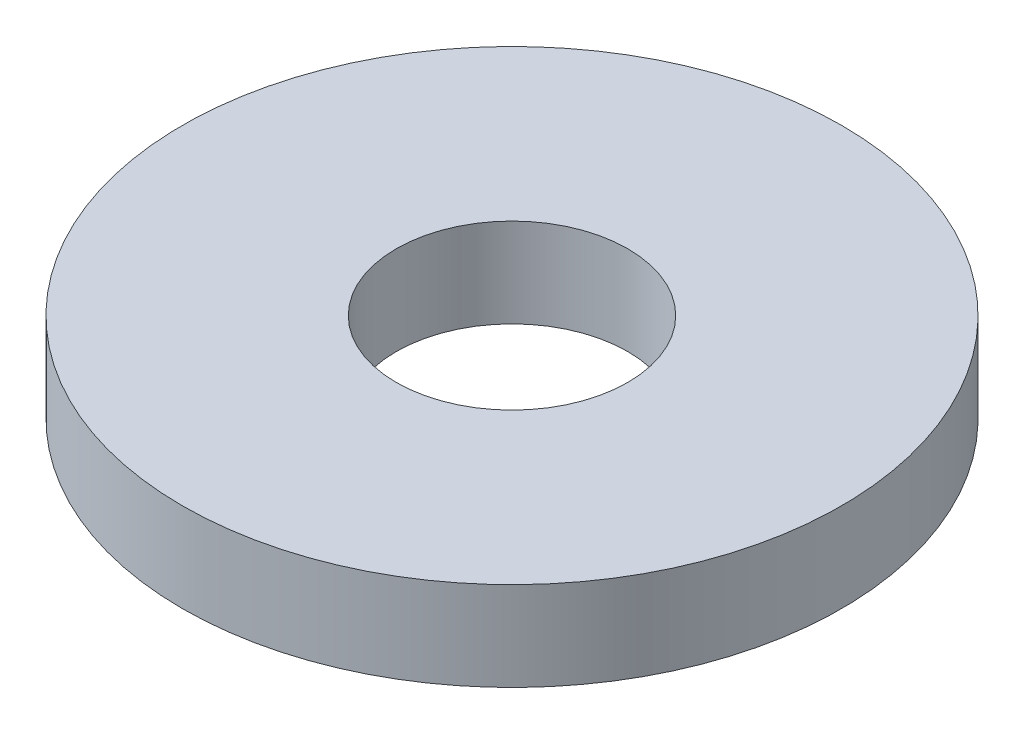
SolidWorks part; units mm, degrees
ref_plane "Front Plane" through (0, 0, 0) normal (0, 0, 1) x (1, 0, 0)
ref_plane "Top Plane" through (0, 0, 0) normal (0, 1, 0) x (1, 0, 0)
ref_plane "Right Plane" through (0, 0, 0) normal (1, 0, 0) x (0, 0, -1)
sketch "Sketch1" plane through (0, 0, 0) normal (0, 1, 0) x (1, 0, 0)
  circle A0 centre (0, 0) radius 92.5
  dimension "FLANGE_OD" = 185
extrude "Boss-Extrude1" add sketch "Sketch1" along normal blind 25
sketch "Sketch2" plane through (0, 0, 0) normal (0, 1, 0) x (1, 0, 0)
  circle A0 centre (0, 0) radius 32.5
  dimension "BORE_D" = 65
extrude "Cut-Extrude1" cut sketch "Sketch2" along normal through all
sketch "Sketch3" plane through (0, 25, 0) normal (0, 1, 0) x (1, 0, 0)
  circle A0 centre (0, 0) radius 28.4485 construction
  circle A1 centre (-28.4485, 0) radius 2.2738
  dimension "BOLT_D" = 4.5476
  dimension "BOLT_PCD" = 56.897
extrude "Cut-Extrude2" cut sketch "Sketch3" against normal blind 15.1801 rebuild error yes
pattern_circular "CirPattern1" count 5 over 360 rebuild error yes
